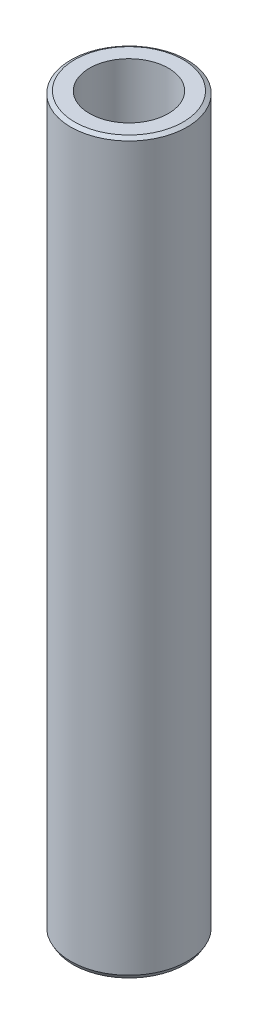
SolidWorks part; units mm, degrees
ref_plane "Front Plane" through (0, 0, 0) normal (0, 0, 1) x (1, 0, 0)
ref_plane "Top Plane" through (0, 0, 0) normal (0, 1, 0) x (1, 0, 0)
ref_plane "Right Plane" through (0, 0, 0) normal (1, 0, 0) x (0, 0, -1)
sketch "Sketch1" plane through (0, 0, 0) normal (0, 1, 0) x (1, 0, 0)
  circle A0 centre (0, 0) radius 47.5
  dimension "SHAFT_OD" = 95
extrude "Boss-Extrude1" add sketch "Sketch1" along normal blind 594.9702
sketch "Sketch2" plane through (0, 0, 0) normal (0, 1, 0) x (1, 0, 0)
  circle A0 centre (0, 0) radius 32.1678
  dimension "BORE_D" = 64.3356
extrude "Cut-Extrude1" cut sketch "Sketch2" along normal through all
chamfer "Chamfer1" distance 1.8951 angle 60 2 edges at (0, 594.9702, 47.5) (0, 0, 47.5) first distance on face at (0, 594.9702, 47.5) first distance on face at (0, 0, 32.1678)
